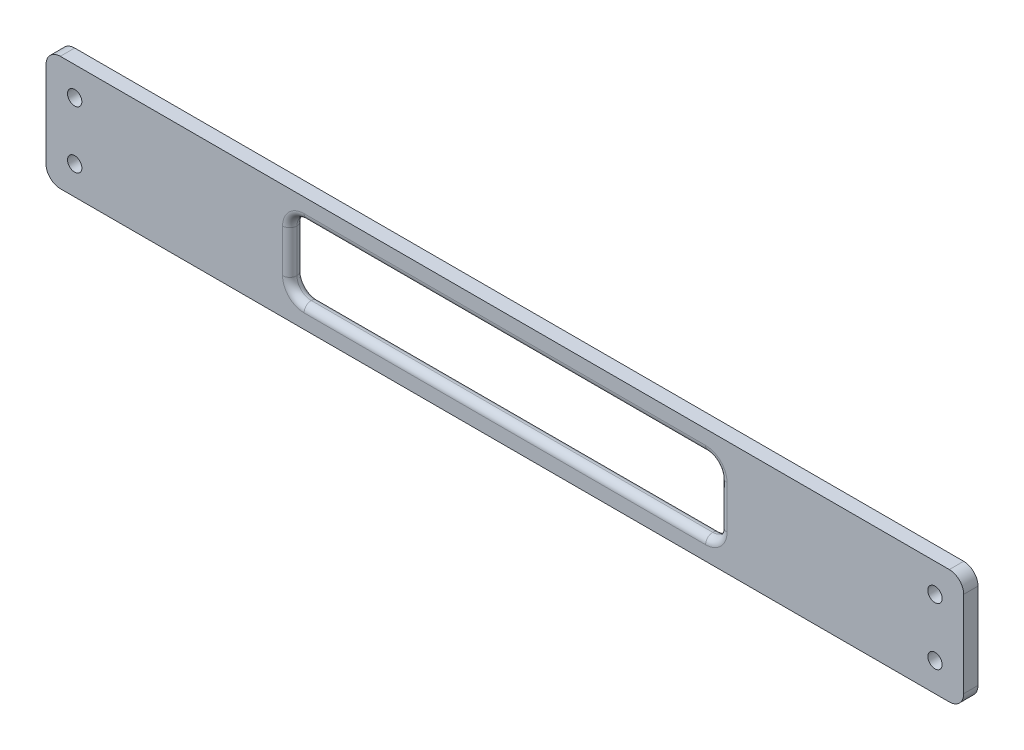
SolidWorks part; units mm, degrees
ref_plane "Front Plane" through (0, 0, 0) normal (0, 0, 1) x (1, 0, 0)
ref_plane "Top Plane" through (0, 0, 0) normal (0, 1, 0) x (1, 0, 0)
ref_plane "Right Plane" through (0, 0, 0) normal (1, 0, 0) x (0, 0, -1)
sketch "Sketch1" plane through (0, 0, 0) normal (0, 0, 1) x (1, 0, 0)
  line L3 (-203.2, -25.4) -> (203.2, -25.4)
  line L4 (-203.2, -25.4) -> (-203.2, 25.4)
  line L5 (-203.2, 25.4) -> (203.2, 25.4)
  line L6 (203.2, -25.4) -> (203.2, 25.4)
  line L7 (-203.2, -25.4) -> (203.2, 25.4) construction
  line L8 (-203.2, 25.4) -> (203.2, -25.4) construction
  point P0 (0, 0)
  dimension "D1" = 406.4
  dimension "D2" = 50.8
extrude "Boss-Extrude1" add sketch "Sketch1" along normal blind 6.35
sketch "Sketch2" plane through (0, 0, 6.35) normal (0, 0, 1) x (1, 0, 0)
  line L1 (-88.9, -15.875) -> (88.9, -15.875)
  line L2 (-95.25, -9.525) -> (-95.25, 9.525)
  line L3 (-88.9, 15.875) -> (88.9, 15.875)
  line L4 (95.25, -9.525) -> (95.25, 9.525)
  line L5 (-95.25, -15.875) -> (95.25, 15.875) construction
  line L6 (-95.25, 15.875) -> (95.25, -15.875) construction
  arc A0 (88.9, 15.875) -> (95.25, 9.525) centre (88.9, 9.525) cw
  arc A1 (88.9, -15.875) -> (95.25, -9.525) centre (88.9, -9.525) ccw
  arc A2 (-88.9, -15.875) -> (-95.25, -9.525) centre (-88.9, -9.525) cw
  arc A3 (-95.25, 9.525) -> (-88.9, 15.875) centre (-88.9, 9.525) cw
  point P0 (0, 0)
  dimension "D3" = 6.35
  dimension "D1" = 190.5
  dimension "D2" = 31.75
extrude "Cut-Extrude1" cut sketch "Sketch2" against normal blind 6.35
fillet "Fillet1" radius 6.35 4 edges at (203.2, -25.4, 3.175) (203.2, 25.4, 3.175) (-203.2, -25.4, 3.175) (-203.2, 25.4, 3.175)
sketch "Sketch3" plane through (0, 0, 6.35) normal (0, 0, 1) x (1, 0, 0)
  line L0 (196.85, 25.4) -> (-196.85, 25.4) construction
  line L1 (-203.2, 19.05) -> (-203.2, -19.05) construction
  line L2 (0, 0) -> (0, 58.4853) construction
  circle A0 centre (-190.5, 12.7) radius 3.175
  circle A1 centre (-190.5, -12.7) radius 3.175
  circle A2 centre (190.5, -12.7) radius 3.175
  circle A3 centre (190.5, 12.7) radius 3.175
  dimension "D1" = 6.35
  dimension "D2" = 6.35
  dimension "D3" = 25.4
  dimension "D4" = 12.7
  dimension "D5" = 12.7
  dimension "D6" = 12.7
extrude "Cut-Extrude2" cut sketch "Sketch3" against normal blind 6.35
fillet "Fillet3" radius 3.175 16 edges at (-93.3901, -14.0151, 0) (-95.25, 0, 0) (-93.3901, 14.0151, 0) (0, 15.875, 0) (93.3901, 14.0151, 0) (95.25, 0, 0) (93.3901, -14.0151, 0) (-93.3901, -14.0151, 6.35) (-95.25, 0, 6.35) (-93.3901, 14.0151, 6.35) (0, 15.875, 6.35) (93.3901, 14.0151, 6.35) (95.25, 0, 6.35) (93.3901, -14.0151, 6.35) (0, -15.875, 0) (0, -15.875, 6.35)
sketch "Sketch4" plane through (0, 0, 6.35) normal (0, 0, 1) x (1, 0, 0)
  line L0 (-196.85, -25.4) -> (196.85, -25.4) construction
  line L1 (-159.9466, -25.4) -> (-134.5466, -25.4)
  line L2 (-159.9466, -25.4) -> (-159.9466, 0)
  line L3 (-159.9466, 0) -> (-134.5466, 0)
  line L4 (-134.5466, -25.4) -> (-134.5466, 0)
  dimension "D1" = 25.4
  dimension "D2" = 25.4
